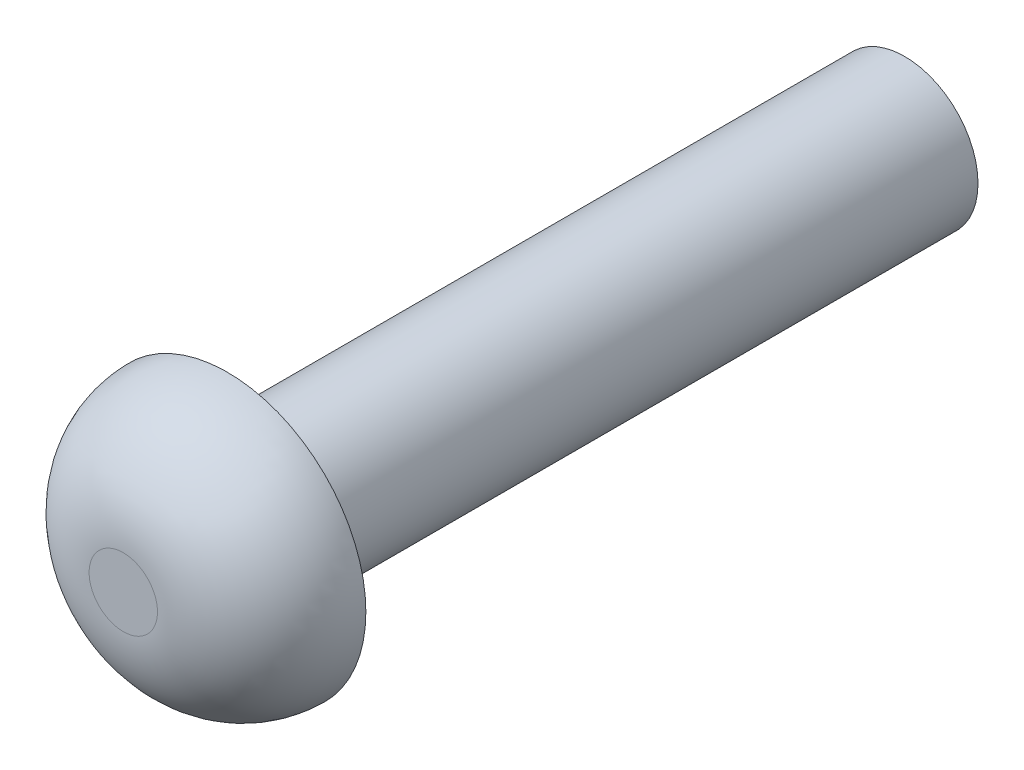
SolidWorks part; units mm, degrees
ref_plane "Plano frontal" through (0, 0, 0) normal (0, 0, 1) x (1, 0, 0)
ref_plane "Plano superior" through (0, 0, 0) normal (0, 1, 0) x (1, 0, 0)
ref_plane "Plano direito" through (0, 0, 0) normal (1, 0, 0) x (0, 0, -1)
sketch "Esboço1" plane through (0, 0, 0) normal (0, 0, 1) x (1, 0, 0)
  circle A0 centre (0, 0) radius 1.125
  dimension "D1" = 2.25
extrude "Ressalto-extrusão1" add sketch "Esboço1" along normal blind 12
sketch "Esboço2" plane through (0, 0, 12) normal (0, 0, 1) x (1, 0, 0)
  circle A0 centre (0, 0) radius 2.125
  circle A1 centre (0, 0) radius 1.125 construction
  dimension "D1" = 1
extrude "Ressalto-extrusão2" add sketch "Esboço2" against normal blind 1.6
fillet "Filete1" radius 1.6 1 edges at (2.125, 0, 12)
